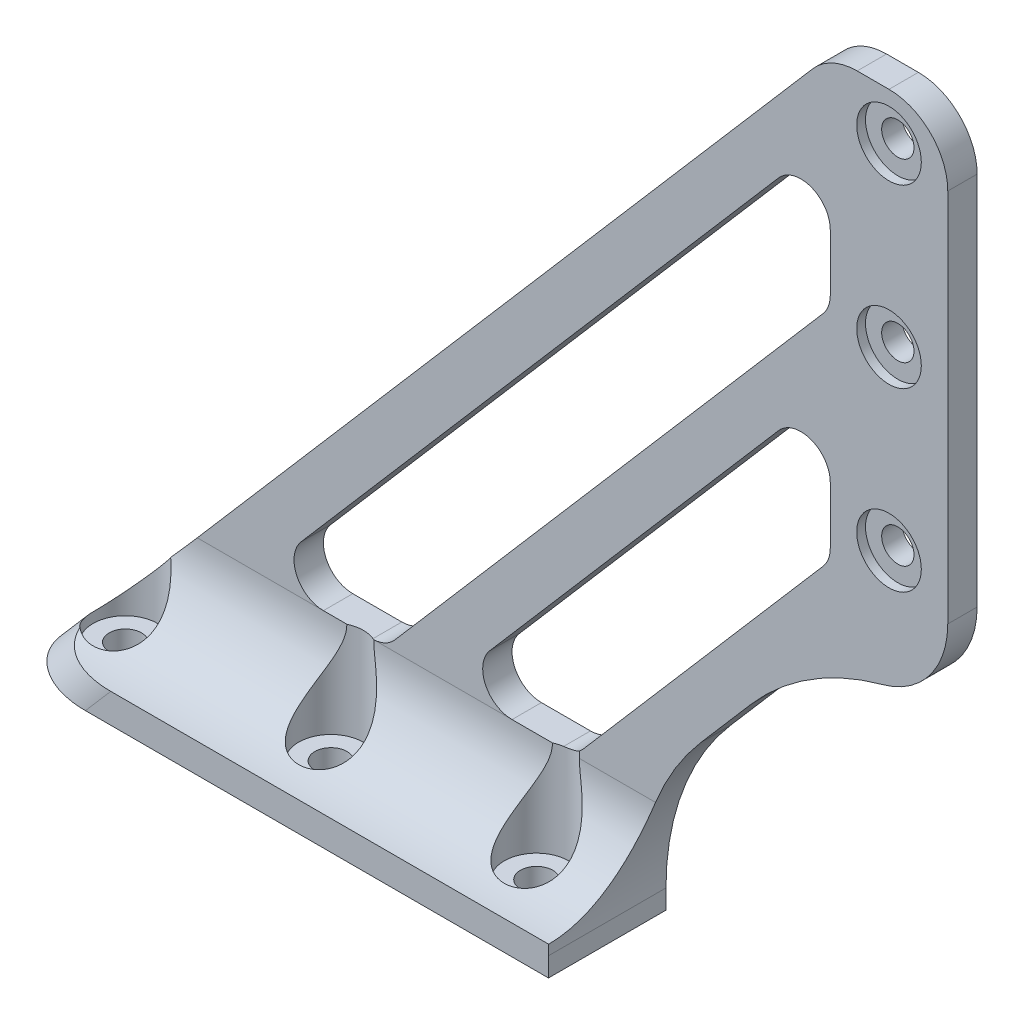
SolidWorks part; units mm, degrees
ref_plane "Front Plane" through (0, 0, 0) normal (0, 0, 1) x (1, 0, 0)
ref_plane "Top Plane" through (0, 0, 0) normal (0, 1, 0) x (1, 0, 0)
ref_plane "Right Plane" through (0, 0, 0) normal (1, 0, 0) x (0, 0, -1)
sketch "Sketch1" plane through (0, 0, 0) normal (0, 0, 1) x (1, 0, 0)
  line L0 (0, 0) -> (-145, 0)
  line L2 (0, 145) -> (0, 0)
  line L3 (0, 145) -> (-20, 145)
  line L4 (-20, 145) -> (-145, 0)
  dimension "D1" = 145
  dimension "D2" = 20
extrude "Boss-Extrude1" add sketch "Sketch1" along normal blind 5
sketch "Sketch4" plane through (0, 0, 0) normal (0, -1, 0) x (1, 0, 0)
  line L1 (-145, 5) -> (0, 5)
  line L2 (-145, 5) -> (-145, 20)
  line L3 (-145, 20) -> (0, 20)
  line L4 (0, 5) -> (0, 20)
  line L5 (-145, 0) -> (0, 0) construction
  dimension "D1" = 20
extrude "Boss-Extrude2" add sketch "Sketch4" against normal blind 5
sketch "Sketch5" plane through (0, 0, 5) normal (0, 0, -1) x (-1, 0, 0)
  line L0 (145, 5) -> (145, 0)
  line L1 (145, 0) -> (140.6897, 5)
  line L2 (140.6897, 5) -> (145, 5)
extrude "Cut-Extrude1" cut sketch "Sketch5" against normal blind 25
sketch "Sketch6" plane through (0, 0, 5) normal (0, 0, 1) x (1, 0, 0)
  line L0 (0, 5) -> (0, 145) construction
  line L1 (0, 145) -> (-20, 145) construction
  circle A0 centre (-10, 137) radius 2.75
  circle A5 centre (-10, 107) radius 2.75
  circle A6 centre (-10, 77) radius 2.75
  dimension "D1" = 5.5
  dimension "D2" = 10
  dimension "D3" = 8
  dimension "D4" = 3
extrude "Cut-Extrude2" cut sketch "Sketch6" against normal blind 25
sketch "Sketch7" plane through (0, 0, 0) normal (0, -1, 0) x (1, 0, 0)
  line L0 (-145, 20) -> (-145, 0) construction
  circle A0 centre (-135, 10) radius 2.75
  circle A3 centre (-100, 10) radius 2.75
  circle A4 centre (-65, 10) radius 2.75
  point P4 (-145, 10)
  dimension "D1" = 5.5
  dimension "D2" = 10
extrude "Cut-Extrude3" cut sketch "Sketch7" against normal blind 25
fillet "Fillet1" radius 15 1 edges at (-70.3448, 5, 5)
fillet "Fillet2" radius 10 4 edges at (0, 145, 2.5) (-20, 145, 2.5) (0, 2.5, 20) (-142.8448, 2.5, 20)
sketch "Sketch8" plane through (0, 0, 0) normal (0, -1, 0) x (1, 0, 0)
  circle A0 centre (-135, 10) radius 5.5
  circle A3 centre (-100, 10) radius 5.5
  circle A4 centre (-65, 10) radius 5.5
  dimension "D1" = 11
extrude "Cut-Extrude4" cut sketch "Sketch8" against normal blind 18 from offset 3.5 offset against normal yes
sketch "Sketch9" plane through (0, 0, 5) normal (0, 0, 1) x (1, 0, 0)
  circle A2 centre (-10, 137) radius 5.5
  circle A3 centre (-10, 107) radius 5.5
  circle A4 centre (-10, 77) radius 5.5
  dimension "D1" = 11
extrude "Cut-Extrude5" cut sketch "Sketch9" against normal offset from surface (1.5 mm away) 3.5 up to face at (-12.75, 137, 0)
sketch "Sketch10" plane through (0, 0, 5) normal (0, 0, 1) x (1, 0, 0)
  line L0 (-117.1963, 20) -> (-20, 132.7477)
  line L2 (-20, 132.7477) -> (-20, 107.7477)
  line L3 (-20, 20) -> (-52.9682, 20) construction
  line L4 (-127.7586, 20) -> (-102.2913, 20) construction
  line L5 (-22.9919, 141.5294) -> (-127.7586, 20) construction
  line L6 (0, 20) -> (0, 135) construction
  line L7 (-95.6446, 20) -> (-20, 107.7477)
  line L8 (-85.0823, 20) -> (-20, 95.4954)
  line L9 (-52.9682, 20) -> (-20, 58.2432)
  line L10 (-63.5305, 20) -> (-20, 70.4954)
  line L11 (-20, 95.4954) -> (-20, 70.4954)
  line L12 (-20, 58.2432) -> (-20, 20) construction
  line L13 (-63.5305, 20) -> (-85.0823, 20)
  line L14 (-95.6446, 20) -> (-117.1963, 20)
  line L15 (-20, 58.2432) -> (0, 58.2432)
  line L16 (0, 58.2432) -> (0, 0)
  line L17 (0, 0) -> (-52.9682, 0)
  line L18 (-10, 0) -> (-131.7971, 0) construction
  line L19 (-52.9682, 0) -> (-52.9682, 20)
  dimension "D1" = 8
  dimension "D2" = 20
  dimension "D3" = 8
  dimension "D4" = 8
  dimension "D5" = 25
  dimension "D6" = 25
extrude "Cut-Extrude6" cut sketch "Sketch10" against normal blind 8 and the other way blind 25
fillet "Fillet3" radius 5 8 edges at (-85.0823, 20, 2.5) (-117.1963, 20, 2.5) (-20, 95.4954, 2.5) (-20, 132.7477, 2.5) (-95.6446, 20, 2.5) (-63.5305, 20, 2.35) (-20, 70.4954, 2.5) (-20, 107.7477, 2.5)
fillet "Fillet4" radius 45 2 edges at (-52.9682, 20, 2.5) (-20, 58.2432, 2.5)
fillet "Fillet5" radius 15 1 edges at (0, 58.2432, 2.5)
